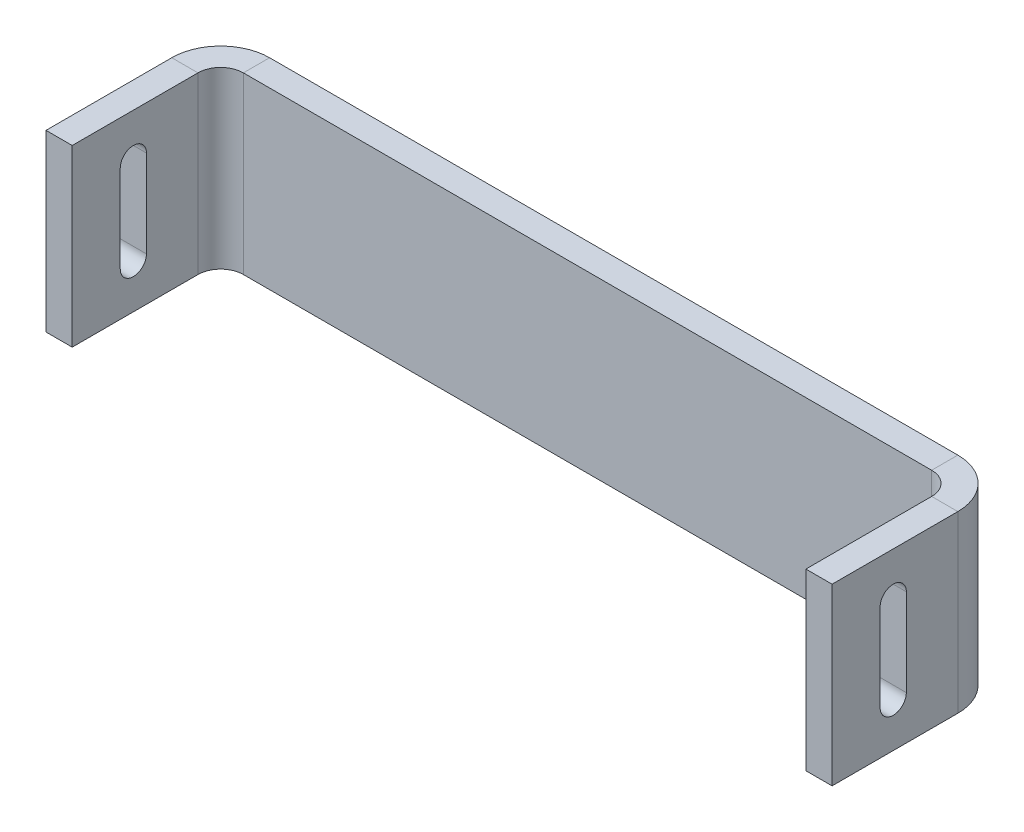
SolidWorks part; units mm, degrees
note: The reader was unsure of these and kept them because the rebuilt part matched: thickness of "Base-Flange1", "Edge-Flange1", "Sheet-Metal1", "Sheet-Metal2", "Sheet-Metal3", "Sheet-Metal4"; flange length of "Edge-Flange1".
material "Alumina"
ref_plane "Front Plane" through (0, 0, 0) normal (0, 0, 1) x (1, 0, 0)
ref_plane "Top Plane" through (0, 0, 0) normal (0, 1, 0) x (1, 0, 0)
ref_plane "Right Plane" through (0, 0, 0) normal (1, 0, 0) x (0, 0, -1)
sketch "Sketch1" plane through (0, 0, 0) normal (0, 0, 1) x (1, 0, 0)
  line L1 (45, 10) -> (-45, 10)
  line L2 (45, 10) -> (45, -10)
  line L3 (45, -10) -> (-45, -10)
  line L4 (-45, 10) -> (-45, -10)
  line L5 (45, 10) -> (-45, -10) construction
  line L6 (45, -10) -> (-45, 10) construction
  point P0 (0, 0)
  dimension "D1" = 90
  dimension "D2" = 20
base flange "Base-Flange1" sketch "Sketch1" thickness 3 reverse thickness direction no parameters "D1"=2.6
edge flange "Edge-Flange1" sketch "Sketch10" flange profiles "Sketch10", "Sketch11" flange angle 90 flange length 20 flange position material inside bend radius 2.6 thickness 3 relief rectangular parameters "D6"=10, "D8"=0.01
sketch "Sketch10" plane through (45, 0, 0) normal (1, 0, 0) x (0, 1, 0)
  line L0 (-10, 0) -> (10, 0) construction
  line L1 (-10, 0) -> (10, 0)
  line L2 (-10, 0) -> (-10, 17)
  line L3 (-10, 17) -> (10, 17)
  line L4 (10, 17) -> (10, 0)
sketch "Sketch11" plane through (-45, 0, 0) normal (-1, 0, 0) x (0, -1, 0)
  line L0 (-10, 0) -> (10, 0) construction
  line L1 (-10, 0) -> (10, 0)
  line L2 (-10, 0) -> (-10, 17)
  line L3 (-10, 17) -> (10, 17)
  line L4 (10, 17) -> (10, 0)
bend "EdgeBend1" bend radius 2.6 bend angle 90 parameters "D5"=1
bend "EdgeBend2" bend radius 2.6 bend angle 90 parameters "D5"=2
sketch "Sketch12" plane through (-45, 0, 0) normal (-1, 0, 0) x (0, 0, 1)
  line L0 (-4.2071, 0) -> (19.1621, 0) construction
  line L1 (10, 5) -> (10, -5) construction
  line L2 (11.5, 5) -> (11.5, -5)
  line L3 (8.5, 5) -> (8.5, -5)
  arc A0 (11.5, 5) -> (8.5, 5) centre (10, 5) ccw
  arc A1 (8.5, -5) -> (11.5, -5) centre (10, -5) ccw
  point P5 (10, 0)
  dimension "D2" = 1.5
  dimension "D1" = 10
  dimension "D3" = 10
extrude "Cut-Extrude1" cut sketch "Sketch12" against normal blind 10 normal cut yes
sketch "Sketch13" plane through (45, 0, 0) normal (1, 0, 0) x (0, 0, -1)
  line L0 (6.0047, 0) -> (-21.5215, 0) construction
  line L1 (-10, 5) -> (-10, -5) construction
  line L2 (-8.5, 5) -> (-8.5, -5)
  line L3 (-11.5, 5) -> (-11.5, -5)
  arc A0 (-8.5, 5) -> (-11.5, 5) centre (-10, 5) ccw
  arc A1 (-11.5, -5) -> (-8.5, -5) centre (-10, -5) ccw
  point P5 (-10, 0)
  dimension "D1" = 1.5
  dimension "D2" = 10
  dimension "D3" = 10
extrude "Cut-Extrude2" cut sketch "Sketch13" against normal blind 10 normal cut yes
sketch "Bend-Lines1" [suppressed] plane through (0, 0, 0) normal (0, 1, 0) x (1, 0, 0)
sketch "Bounding-Box1" [suppressed] plane through (0, 0, 0) normal (0, 1, 0) x (1, 0, 0)
sheet metal parameters "Sheet-Metal1" thickness 3 parameters "D1"=2.6, "D7"=5
flat pattern "Flat-Pattern1" [suppressed]
sketch "Bend-Lines2" plane through (0, 0, 0) normal (0, 1, 0) x (1, 0, 0)
sketch3d "Bounding-Box2" [suppressed]
  line L0 (45, -10, 0) -> (-45, -10, 0) construction
  line L1 (45, 10, 0) -> (-45, 10, 0) construction
  line L2 (45, -10, 0) -> (45, 10, 0) construction
  line L3 (-45, -10, 0) -> (-45, 10, 0) construction
sheet metal parameters "Sheet-Metal2" thickness 3 parameters "D1"=2.6, "D7"=5
flat pattern "Flat-Pattern1"
sketch "Bend-Lines2" plane through (0, 0, 0) normal (0, 0, 1) x (1, 0, 0)
  line L0 (-42.6201, 10) -> (-42.6201, -10) construction
  line L1 (42.6201, -10) -> (42.6201, 10) construction
  line L2 (-42.6201, 10) -> (-42.6201, -10) construction
  line L3 (42.6201, -10) -> (42.6201, 10) construction
sketch3d "Bounding-Box2" [suppressed]
  line L0 (-60.2403, -10, 0) -> (60.2403, -10, 0) construction
  line L1 (-60.2403, 10, 0) -> (60.2403, 10, 0) construction
  line L2 (-60.2403, -10, 0) -> (-60.2403, 10, 0) construction
  line L3 (60.2403, -10, 0) -> (60.2403, 10, 0) construction
bend of the flat pattern "Flatten-<EdgeBend1>1"
bend of the flat pattern "Flatten-<EdgeBend2>1"
sheet metal parameters "Sheet-Metal3" thickness 3 parameters "D1"=2.6, "D7"=5
flat pattern "Flat-Pattern1"
sketch "Bend-Lines2" plane through (0, 0, 0) normal (0, 0, 1) x (1, 0, 0)
  line L0 (-42.6201, 10) -> (-42.6201, -10) construction
  line L1 (42.6201, -10) -> (42.6201, 10) construction
  line L2 (-42.6201, 10) -> (-42.6201, -10) construction
  line L3 (42.6201, -10) -> (42.6201, 10) construction
sketch3d "Bounding-Box2" [suppressed]
  line L0 (-60.2403, -10, 0) -> (60.2403, -10, 0) construction
  line L1 (-60.2403, 10, 0) -> (60.2403, 10, 0) construction
  line L2 (-60.2403, -10, 0) -> (-60.2403, 10, 0) construction
  line L3 (60.2403, -10, 0) -> (60.2403, 10, 0) construction
bend of the flat pattern "Flatten-<EdgeBend1>1"
bend of the flat pattern "Flatten-<EdgeBend2>1"
sheet metal parameters "Sheet-Metal4" thickness 3 parameters "D1"=2.6, "D7"=5
flat pattern "Flat-Pattern1"
sketch "Bend-Lines2" plane through (0, 0, 0) normal (0, 0, 1) x (1, 0, 0)
  line L0 (-42.6201, 10) -> (-42.6201, -10) construction
  line L1 (42.6201, -10) -> (42.6201, 10) construction
  line L2 (-42.6201, 10) -> (-42.6201, -10) construction
  line L3 (42.6201, -10) -> (42.6201, 10) construction
sketch3d "Bounding-Box2" [suppressed]
  line L0 (-60.2403, -10, 0) -> (60.2403, -10, 0) construction
  line L1 (-60.2403, 10, 0) -> (60.2403, 10, 0) construction
  line L2 (-60.2403, -10, 0) -> (-60.2403, 10, 0) construction
  line L3 (60.2403, -10, 0) -> (60.2403, 10, 0) construction
bend of the flat pattern "Flatten-<EdgeBend1>1"
bend of the flat pattern "Flatten-<EdgeBend2>1"
